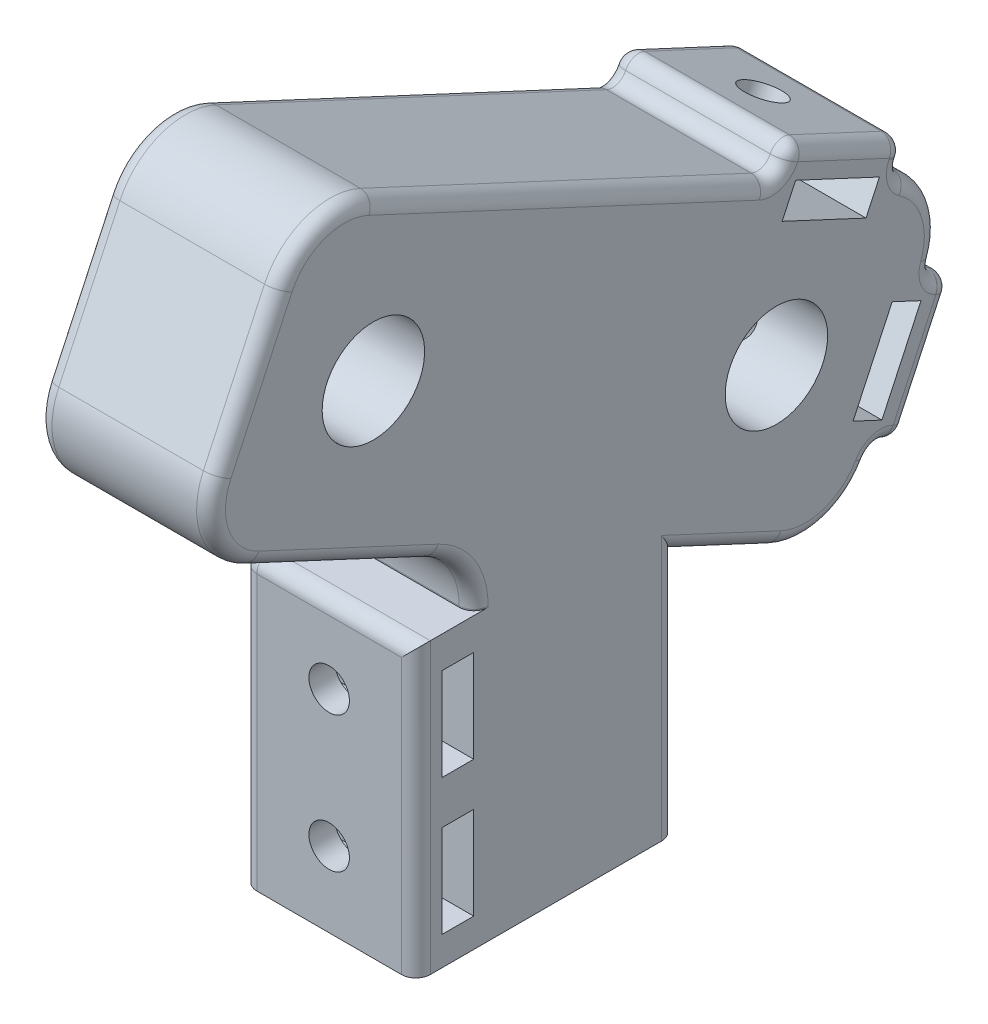
SolidWorks part; units mm, degrees
ref_plane "Front Plane" through (0, 0, 0) normal (0, 0, 1) x (1, 0, 0)
ref_plane "Top Plane" through (0, 0, 0) normal (0, 1, 0) x (1, 0, 0)
ref_plane "Right Plane" through (0, 0, 0) normal (1, 0, 0) x (0, 0, -1)
sketch "Sketch2" plane through (0, 0, 0) normal (1, 0, 0) x (0, 0, -1)
  line L0 (34.0546, -1.867) -> (-23.3201, 24.8872)
  line L1 (-23.3201, 24.8872) -> (-34.0546, 1.867)
  line L2 (-34.0546, 1.867) -> (23.3201, -24.8872)
  line L3 (23.3201, -24.8872) -> (34.0546, -1.867)
  line L4 (-34.0546, 1.867) -> (34.0546, -1.867) construction
  line L5 (-23.3201, 24.8872) -> (23.3201, -24.8872) construction
  line L6 (-144.3239, 0) -> (144.3239, 0) construction
  line L7 (-17.7029, 8.255) -> (17.7029, -8.255) construction
  circle A0 centre (-17.7029, 8.255) radius 4.5
  circle A1 centre (17.7029, -8.255) radius 4.5
  point P2 (0, 0)
  point P9 (0, 0)
  point P16 (0, 0)
  dimension "D3" = 35.4058
  dimension "D4" = 9
  dimension "D5" = 7.62
  dimension "D1" = 25
  dimension "D2" = 25.4
extrude "Boss-Extrude2" add sketch "Sketch2" along normal blind 15.24
sketch "Sketch3" plane through (15.24, 0, 0) normal (1, 0, 0) x (0, 0, -1)
  line L5 (-17.7029, 8.255) -> (-17.7029, -5.7579) construction
  line L6 (-34.0546, 1.867) -> (23.3201, -24.8872) construction
  line L7 (17.7029, -8.255) -> (17.7029, -22.2679) construction
  line L8 (-17.7029, -5.7579) -> (17.7029, -5.7579) construction
  line L9 (-8.89, -9.8674) -> (-8.89, -39.4129)
  line L10 (-8.89, -39.4129) -> (8.89, -39.4129)
  line L11 (8.89, -39.4129) -> (8.89, -18.1584)
  line L12 (8.89, -18.1584) -> (-8.89, -9.8674)
  point P6 (0, -14.0129)
  point P15 (0, -5.7579)
  dimension "D1" = 17.78
  dimension "D2" = 25.4
extrude "Boss-Extrude3" add sketch "Sketch3" against normal up to surface (15.24 mm away) up to face at (0, 0, 0)
sketch "Sketch4" plane through (0, -39.4129, 0) normal (0, -1, 0) x (1, 0, 0)
  line L0 (0, 8.89) -> (15.24, 8.89) construction
  line L1 (2.54, 6.35) -> (12.7, 6.35)
  line L2 (2.54, 6.35) -> (2.54, -6.35)
  line L3 (2.54, -6.35) -> (12.7, -6.35)
  line L4 (12.7, 6.35) -> (12.7, -6.35)
  line L5 (2.54, 6.35) -> (12.7, -6.35) construction
  line L6 (2.54, -6.35) -> (12.7, 6.35) construction
  line L7 (0, -8.89) -> (15.24, -8.89) construction
  line L8 (15.24, 8.89) -> (15.24, -8.89) construction
  line L9 (0, -8.89) -> (0, 8.89) construction
  point P0 (7.62, 0)
  dimension "D1" = 2.54
  dimension "D2" = 2.54
  dimension "D3" = 2.54
  dimension "D4" = 2.54
  dimension "D5" = 10.16
  dimension "D6" = 12.7
extrude "Cut-Extrude1" cut sketch "Sketch4" against normal blind 38.1
sketch "Sketch6" plane through (0, 0, 8.89) normal (0, 0, 1) x (1, 0, 0)
  line L0 (15.24, -9.8674) -> (15.24, -39.4129) construction
  line L1 (0, -39.4129) -> (15.24, -39.4129)
  line L2 (0, -39.4129) -> (0, -14.0129)
  line L3 (0, -14.0129) -> (15.24, -14.0129)
  line L4 (15.24, -39.4129) -> (15.24, -14.0129)
  dimension "D1" = 25.4
extrude "Boss-Extrude4" add sketch "Sketch6" along normal blind 5.08
sketch "Sketch7" plane through (0, 0, 0) normal (-1, 0, 0) x (0, 0, 1)
  line L0 (8.89, -14.0129) -> (8.89, -9.8674) construction
  line L1 (8.89, -28.7449) -> (11.684, -28.7449)
  line L2 (8.89, -28.7449) -> (8.89, -36.8729)
  line L3 (8.89, -36.8729) -> (11.684, -36.8729)
  line L4 (11.684, -28.7449) -> (11.684, -36.8729)
  line L5 (8.89, -28.7449) -> (11.684, -36.8729) construction
  line L6 (8.89, -36.8729) -> (11.684, -28.7449) construction
  line L7 (13.97, -14.0129) -> (13.97, -39.4129) construction
  line L8 (13.97, -14.0129) -> (13.97, -39.4129) construction
  line L9 (8.89, -16.8069) -> (11.684, -16.8069)
  line L10 (8.89, -16.8069) -> (8.89, -24.9349)
  line L11 (8.89, -24.9349) -> (11.684, -24.9349)
  line L12 (11.684, -16.8069) -> (11.684, -24.9349)
  line L13 (8.89, -16.8069) -> (11.684, -24.9349) construction
  line L14 (8.89, -24.9349) -> (11.684, -16.8069) construction
  line L15 (-8.89, -39.4129) -> (13.97, -39.4129) construction
  point P0 (10.287, -32.8089)
  point P10 (10.287, -20.8709)
  dimension "D1" = 8.128
  dimension "D2" = 2.794
  dimension "D3" = 2.54
  dimension "D4" = 3.81
extrude "Cut-Extrude2" cut sketch "Sketch7" against normal up to surface (15.24 mm away) up to face at (15.24, 8.255, 13.2029)
sketch "Sketch8" plane through (0, 0, 13.97) normal (0, 0, 1) x (1, 0, 0)
  line L4 (15.24, -16.8069) -> (0, -16.8069)
  line L5 (0, -16.8069) -> (0, -24.9349)
  line L6 (0, -24.9349) -> (15.24, -24.9349)
  line L7 (15.24, -24.9349) -> (15.24, -16.8069)
  line L12 (15.24, -16.8069) -> (0, -16.8069) construction
  line L13 (0, -16.8069) -> (0, -24.9349) construction
  line L14 (0, -24.9349) -> (15.24, -24.9349) construction
  line L15 (15.24, -24.9349) -> (15.24, -16.8069) construction
  line L16 (15.24, -28.7449) -> (0, -28.7449)
  line L17 (0, -28.7449) -> (0, -36.8729)
  line L18 (0, -36.8729) -> (15.24, -36.8729)
  line L19 (15.24, -36.8729) -> (15.24, -28.7449)
  line L20 (15.24, -28.7449) -> (0, -28.7449) construction
  line L21 (0, -28.7449) -> (0, -36.8729) construction
  line L22 (0, -36.8729) -> (15.24, -36.8729) construction
  line L23 (15.24, -36.8729) -> (15.24, -28.7449) construction
  circle A2 centre (7.62, -32.8089) radius 1.778
  circle A4 centre (7.62, -20.8709) radius 1.778
  point P13 (7.62, -24.9349)
  point P16 (7.62, -28.7449)
  point P18 (0, -20.8709)
  point P20 (0, -32.8089)
  dimension "D2" = 0
  dimension "D3" = 3.556
  dimension "D1" = 0
extrude "Cut-Extrude3" cut sketch "Sketch8" against normal up to surface (20.32 mm away) up to face at (7.62, -20.3629, -6.35)
sketch "Sketch9" plane through (0, 0, 0) normal (-1, 0, 0) x (0, 0, 1)
  line L0 (-17.8906, 5.6704) -> (-18.9641, 7.9724)
  line L1 (-34.0546, -1.867) -> (23.3201, 24.8872) construction
  line L2 (-18.9641, 7.9724) -> (-29.3232, 3.1419)
  line L3 (-29.3232, 3.1419) -> (-28.2497, 0.8398)
  line L4 (-28.2497, 0.8398) -> (-17.8906, 5.6704)
  line L5 (-31.1026, -8.1976) -> (-33.4046, -9.271)
  line L6 (-23.3201, -24.8872) -> (-34.0546, -1.867) construction
  line L7 (-33.4046, -9.271) -> (-28.5741, -19.6301)
  line L8 (-28.5741, -19.6301) -> (-26.2721, -18.5567)
  line L9 (-26.2721, -18.5567) -> (-31.1026, -8.1976)
  line L10 (-23.0702, 3.2551) -> (-17.7029, -8.255) construction
  line L11 (-17.7029, -8.255) -> (-28.6874, -13.3771) construction
  circle A0 centre (-17.7029, -8.255) radius 4.5 construction
  circle A1 centre (-17.7029, -8.255) radius 4.5 construction
  point P18 (-23.0702, 3.2551)
  dimension "D1" = 11.43
  dimension "D2" = 2.54
extrude "Boss-Extrude5" add sketch "Sketch9" against normal up to surface (15.24 mm away) up to face at (15.24, -32.8089, 10.287)
sketch "Sketch10" plane through (0, 0, 0) normal (-1, 0, 0) x (0, 0, 1)
  line L0 (-19.3869, 4.9726) -> (-26.7534, 1.5376)
  line L1 (-26.7534, 1.5376) -> (-25.5726, -0.9946)
  line L2 (-25.5726, -0.9946) -> (-18.2061, 2.4404)
  line L3 (-18.2061, 2.4404) -> (-19.3869, 4.9726)
  line L4 (-30.4049, -9.6939) -> (-26.9698, -17.0604)
  line L5 (-26.9698, -17.0604) -> (-24.4376, -15.8796)
  line L6 (-24.4376, -15.8796) -> (-27.8727, -8.5131)
  line L7 (-27.8727, -8.5131) -> (-30.4049, -9.6939)
  line L8 (-18.9641, 7.9724) -> (-29.3232, 3.1419) construction
  line L9 (-33.4046, -9.271) -> (-28.5741, -19.6301) construction
  line L10 (-33.4046, -9.271) -> (-28.5741, -19.6301) construction
  line L11 (-18.9641, 7.9724) -> (-29.3232, 3.1419) construction
  line L12 (-23.0702, 3.2551) -> (-24.1436, 5.5571) construction
  line L13 (-30.9894, -14.4506) -> (-28.6874, -13.3771) construction
  point P16 (-28.6874, -13.3771)
  dimension "D1" = 8.128
  dimension "D2" = 2.54
  dimension "D3" = 2.794
extrude "Cut-Extrude4" cut sketch "Sketch10" against normal up to surface (15.24 mm away) up to face at (15.24, -32.8089, 10.287)
sketch "Sketch11" plane through (0, -14.4506, -30.9894) normal (0, -0.4226, -0.9063) x (-1, 0, 0)
  line L4 (0, 5.715) -> (-15.24, 5.715)
  line L5 (-15.24, 5.715) -> (-15.24, -5.715)
  line L6 (-15.24, -5.715) -> (0, -5.715)
  line L7 (0, -5.715) -> (0, 5.715)
  line L9 (-15.24, 5.715) -> (-15.24, -5.715) construction
  line L10 (-15.24, -5.715) -> (0, -5.715) construction
  line L11 (0, -5.715) -> (0, 5.715) construction
  circle A0 centre (-7.62, 0) radius 1.778
  point P9 (-7.62, -5.715)
  dimension "D2" = 3.556
  dimension "D1" = 0
extrude "Cut-Extrude5" cut sketch "Sketch11" against normal up to surface (10.5261 mm away) up to face at (15.24, -8.255, -22.2029)
sketch "Sketch12" plane through (0, 13.8121, -6.4407) normal (0, 0.9063, -0.4226) x (1, 0, 0)
  line L4 (0, 13.818) -> (15.24, 13.818)
  line L5 (15.24, 13.818) -> (15.24, 25.248)
  line L6 (15.24, 25.248) -> (0, 25.248)
  line L7 (0, 25.248) -> (0, 13.818)
  line L8 (0, 13.818) -> (15.24, 13.818) construction
  line L9 (15.24, 13.818) -> (15.24, 25.248) construction
  line L11 (0, 25.248) -> (0, 13.818) construction
  circle A0 centre (7.62, 19.533) radius 1.778
  point P7 (7.62, 13.818)
  point P8 (15.24, 19.533)
  dimension "D2" = 3.556
  dimension "D1" = 0
extrude "Cut-Extrude6" cut sketch "Sketch12" against normal up to surface (11.1061 mm away) up to face at (7.3551, -11.5991, -20.7141)
fillet "Fillet1" radius 6.35 5 edges at (7.62, -24.8872, -23.3201) (7.62, -1.867, -34.0546) (7.62, 24.8872, 23.3201) (7.62, 1.867, 34.0546) (7.62, -9.8674, 8.89)
fillet "Fillet2" radius 1.27 32 edges at (0, -13.9629, 8.89) (0, -10.501, 9.8845) (0, -4.4872, 20.428) (0, 2.7666, 31.583) (0, 13.3771, 28.6874) (0, 22.4156, 22.4205) (0, -2.7666, -31.583) (0, -22.4156, -22.4205) (0, -20.181, -13.2275) (15.24, 22.4156, 22.4205) (15.24, 13.3771, 28.6874) (15.24, 2.7666, 31.583) (15.24, -4.4872, 20.428) (15.24, -10.501, 9.8845) (15.24, -13.9629, 8.89) (0, -28.7856, -8.89) (0, -26.7129, 13.97) (15.24, 13.937, -0.1628) (15.24, 6.8214, -18.4273) (0, -19.0934, -27.4231) (0, 1.9909, -28.7864) (0, -8.7343, -32.2536) (0, 6.8214, -18.4273) (0, 13.937, -0.1628) (7.62, 7.9724, -18.9641) (7.62, 3.1419, -29.3232) (7.62, -9.271, -33.4046) (7.62, -19.6301, -28.5741) (7.62, 5.6704, -17.8906) (7.62, 0.8398, -28.2497) (7.62, -18.5567, -26.2721) (7.62, -8.1976, -31.1026)
fillet "Fillet3" radius 1.27 23 edges at (0, -14.0129, 10.16) (0.372, -14.0129, 13.598) (0.372, 7.4781, -19.144) (0.372, 2.9619, -28.8288) (15.24, -20.181, -13.2275) (15.24, -22.501, -22.1698) (15.24, -19.0227, -26.4781) (15.24, -19.0878, -27.4111) (15.24, -19.1358, -28.3942) (15.24, -14.4506, -30.9894) (15.24, -9.451, -32.9103) (15.24, -8.7287, -32.2416) (15.24, -8.0559, -31.5921) (14.868, 7.4781, -19.144) (15.24, 5.5571, -24.1436) (15.24, 2.9619, -28.8288) (15.24, 1.9467, -28.7658) (15.24, 1.0282, -28.6719) (8.255, -14.0129, 13.97) (15.24, -26.7129, 13.97) (15.24, -28.7856, -8.89) (0, 5.5571, -24.1436) (15.24, -2.997, -31.6619)
fillet "Fillet4" radius 1.27 4 edges at (7.62, -39.4129, 6.35) (2.54, -39.4129, 0) (7.62, -39.4129, -6.35) (12.7, -39.4129, 0)
